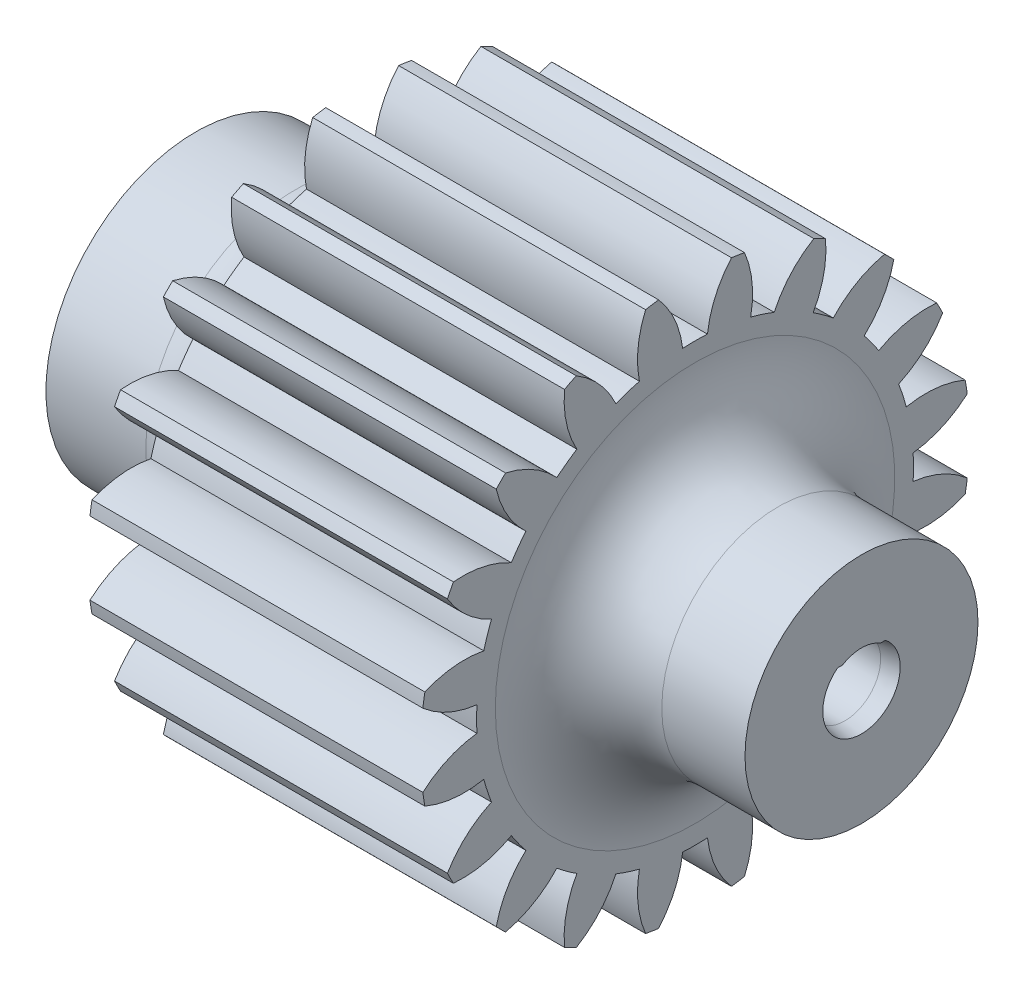
SolidWorks part; units mm, degrees
ref_plane "Plane1" through (0, 0, 0) normal (0, 0, 1) x (1, 0, 0)
ref_plane "Plane2" through (0, 0, 0) normal (0, 1, 0) x (1, 0, 0)
ref_plane "Plane3" through (0, 0, 0) normal (1, 0, 0) x (0, 0, -1)
other "Configuration Table"
sketch "HoldingSke" plane through (0, 0, 0) normal (0, 1, 0) x (1, 0, 0)
  line L0 (0, 0) -> (0.6265, -0.228)
  line L1 (-15, 0) -> (100, 0) construction
  line L2 (0, 0) -> (-2.1039, 2.3779)
  line L3 (0, 0) -> (-11.863, 4.5341)
  line L4 (0, 0) -> (8.1152, 2.9537)
  line L5 (0, 0) -> (-46.8476, -17.4728)
  line L6 (0, 0) -> (-16.5793, -11.1861)
  line L7 (-2.1039, 2.3779) -> (8.6586, 51.2059)
  line L8 (-76.2, 54.61) -> (-75.5, 54.61)
  line L9 (-71.009, 38.7566) -> (-53.1078, 45.2721)
  line L10 (-76.2, 71.12) -> (104.1128, 71.12)
  line L11 (0, 0) -> (-20, 0)
  line L12 (-76.2, 101.6) -> (-76.147, 101.6)
  line L13 (24.9733, 27.94) -> (52.9518, 28.4284)
  line L14 (24.9733, 27.94) -> (24.9743, 27.94)
  line L15 (24.9733, 27.94) -> (100.4006, 29.5858)
  line L16 (-63.627, -1.5) -> (-12.827, -1.5)
  circle A0 centre (0, 0) radius 2
  circle A1 centre (0, 0) radius 13.124
  circle A2 centre (0, 0) radius 37.5
  circle A3 centre (0, 0) radius 2
  dimension "Num_teeth" = 20
  dimension "Pitch_radius" = 180.3128
  dimension "Width" = 20
  dimension "Thickness" = 20
sketch "BasProSke" plane through (0, 0, 0) normal (0, 1, 0) x (1, 0, 0)
  line L0 (-10, 0) -> (60, 0) construction
  line L1 (0, 0) -> (0, 16.5)
  line L2 (0, 0) -> (20, 0)
  line L3 (20, 0) -> (20, 16.5)
  line L4 (20, 16.5) -> (0, 16.5)
  dimension "Thickness" = 20
  dimension "Diameter" = 33
revolve "Base-Revolve" add sketch "BasProSke" angle 360 about L0
sketch "TooCutSke" plane through (0, 0, 0) normal (1, 0, 0) x (0, 0, -1)
  line L1 (0, 0) -> (0, 107) construction
  line L2 (0, 0) -> (-1.2696, 14.9462) construction
  line L3 (0, 0) -> (-4.6808, 29.5532) construction
  line L4 (-1.2696, 14.9462) -> (-2.3404, 14.7766) construction
  arc A0 (0.7438, 13.1029) -> (-0.7438, 13.1029) centre (0, 0) ccw
  arc A1 (2.21, 16.377) -> (-2.21, 16.377) centre (0, 0) ccw
  circle A2 centre (0, 0) radius 15 construction
  circle A3 centre (0, 0) radius 14.0954 construction
  arc A4 (-0.7438, 13.1029) -> (-2.21, 16.377) centre (-6.7025, 12.3999) ccw
  arc A5 (2.21, 16.377) -> (0.7438, 13.1029) centre (6.7025, 12.3999) ccw
extrude "ToothCut" cut sketch "TooCutSke" along normal through all
fillet "Breaks" [suppressed] radius 0.03 tangent propagation no
fillet "RootFillets" [suppressed] radius 0.376
pattern_circular "TeethCuts" count 20 every 18 about axis through (-10, 0, 0) along (1, 0, 0) of "ToothCut", "RootFillets", "Breaks"
sketch "HubNeaOneSke" plane through (0, 0, 0) normal (-1, 0, 0) x (0, 0, 1)
  circle A0 centre (0, 0) radius 13.124
  dimension "Diameter" = 26.248
extrude "HubNearOne" [suppressed] add sketch "HubNeaOneSke" along normal blind 30.0001
sketch "HubNeaBotSke" plane through (0, 0, 0) normal (-1, 0, 0) x (0, 0, 1)
  circle A0 centre (0, 0) radius 13.124
  dimension "Diameter" = 26.248
extrude "HubNearBoth" [suppressed] add sketch "HubNeaBotSke" along normal blind 15
ref_plane "FarPln" through (20, 0, 0) normal (1, 0, 0) x (0, 0, -1)
sketch "HubFarSke" plane through (20, 0, 0) normal (1, 0, 0) x (0, 0, -1)
  circle A0 centre (0, 0) radius 13.124
  dimension "Diameter" = 26.248
extrude "HubFar" [suppressed] add sketch "HubFarSke" along normal blind 15
sketch "BorSke" plane through (0, 0, 0) normal (1, 0, 0) x (0, 0, -1)
  circle A0 centre (0, 0) radius 0.5
  dimension "Diameter" = 1
extrude "Bore" cut sketch "BorSke" along normal mid plane 100.0001
sketch "KeySke" plane through (0, 0, 0) normal (1, 0, 0) x (0, 0, -1)
  line L0 (-0.8, 0) -> (-0.8, 2.7)
  line L1 (-0.8, 2.7) -> (0.8, 2.7)
  line L2 (0.8, 2.7) -> (0.8, 0)
  line L3 (0, 0) -> (0, 34) construction
  line L4 (-0.8, 0) -> (0.8, 0)
  dimension "Width" = 1.6
extrude "Keyway" [suppressed] cut sketch "KeySke" along normal mid plane 100.0001
pattern_circular "Keyway2" [suppressed] count 2 every 90 about axis through (-10, 0, 0) along (1, 0, 0) reverse direction yes
sketch "Sketch1" plane through (20, 0, 0) normal (1, 0, 0) x (0, 0, -1)
  circle A0 centre (0, 0) radius 7
  circle A1 centre (0, 0) radius 0.5
  circle A2 centre (0, 0) radius 0.5 construction
  dimension "D1" = 14
extrude "Boss-Extrude1" add sketch "Sketch1" along normal blind 10
fillet "Fillet1" radius 5 1 edges at (20, 0, 7)
sketch "Sketch2" plane through (0, 0, 0) normal (-1, 0, 0) x (0, 0, 1)
  circle A0 centre (0, 0) radius 9
  dimension "D1" = 18
extrude "Boss-Extrude2" add sketch "Sketch2" along normal up to surface (10 mm away)
sketch "Sketch3" plane through (-10, 0, 0) normal (-1, 0, 0) x (0, 0, 1)
  circle A0 centre (0, 0) radius 3
  dimension "D1" = 6
extrude "Boss-Extrude3" add sketch "Sketch3" along normal up to surface (3.2 mm away)
fillet "Fillet2" radius 4 1 edges at (0, 0, -9)
sketch "Sketch4" plane through (30, 0, 0) normal (1, 0, 0) x (0, 0, -1)
  line L0 (-1.3229, 1.5) -> (1.3229, 1.5) construction
  line L1 (-1.3784, 1.65) -> (1.3784, 1.65)
  arc A2 (-1.3229, 1.5) -> (1.3229, 1.5) centre (0, 0) ccw construction
  arc A3 (-1.3784, 1.65) -> (1.3784, 1.65) centre (0, 0) ccw
  point P4 (0, -2)
  dimension "D1" = 4
  dimension "D2" = 3.5
  dimension "D3" = 0.15
extrude "Cut-Extrude1" cut sketch "Sketch4" against normal blind 25 contours A3 L1
chamfer "Chamfer2" distance 1 angle 10 2 edges at (30, -2.15, 0) (30, 1.65, 0) first distance on face at (17.5, -0.25, 0) first distance on face at (17.5, 1.65, 0)
sketch "Sketch5" plane through (30, 0, 0) normal (1, 0, 0) x (0, 0, -1)
  circle A0 centre (0, 0) radius 2.15
extrude "Cut-Extrude2" cut sketch "Sketch5" against normal blind 3
equation "' \"Module@HoldingSke\" = 6.35"
equation "' \"Num_teeth@HoldingSke\" = 12"
equation "' \"Ap@HoldingSke\" =  20"
equation "' \"Ap@HoldingSke\" = 20"
equation "' \"Width@HoldingSke\" = 0.5 * 25.4"
equation "' \"Hub_dia@HoldingSke\"= 1 * 25.4"
equation "' \"Hub_dia@HoldingSke\" = 1 * 25.4"
equation "' \"Overall_len@HoldingSke\" = 1.0 * 25.4"
equation "' \"Bore@HoldingSke\" = 0.75 * 25.4"
equation "' \"T_dim@HoldingSke\" = 0.1 * 25.4"
equation "' \"Width@KeySke\" = 0.25 * 25.4"
equation "' \"Show_teeth@HoldingSke\" = 13"
equation "' \"Backlash@HoldingSke\" = 0.009 * 25.4"
equation "' \"Addendum_fac@HoldingSke\" = 1.0"
equation "' \"Dedendum_fac@HoldingSke\" = 1.25"
equation "' \"Dedendum_add@HoldingSke\" = 0.00005 * 25.4"
equation "' \"Clearance_fac@HoldingSke\" = 0.25"
equation "\"Pitch@HoldingSke\" = 1 / \"Module@HoldingSke\""
equation "\"Overcut_dia@TooCutSke\" = (\"Num_teeth@HoldingSke\" + 2 * \"Addendum_fac@HoldingSke\") / \"Pitch@HoldingSke\" + 0.002 * 25.4"
equation "\"Pitch_dia@TooCutSke\" = \"Num_teeth@HoldingSke\" / \"Pitch@HoldingSke\""
equation "\"Base_dia@TooCutSke\" = \"Num_teeth@HoldingSke\" / \"Pitch@HoldingSke\" * cos((\"Ap@HoldingSke\"  * 3.14159265 / 180))"
equation "\"Root_dia@TooCutSke\" = (\"Num_teeth@HoldingSke\" + 2) / \"Pitch@HoldingSke\" - 2 * (\"Addendum_fac@HoldingSke\" + \"Dedendum_fac@HoldingSke\") / \"Pitch@HoldingSke\" - \"Dedendum_add@HoldingSke\" * 2"
equation "\"Half_ang@TooCutSke\" = 180 / \"Num_teeth@HoldingSke\""
equation "\"Half_CT@TooCutSke\" = \"Num_teeth@HoldingSke\" / \"Pitch@HoldingSke\" * sin((3.14159265 / 2 / \"Num_teeth@HoldingSke\")) / 2 - 7 * \"Backlash@HoldingSke\" / 4"
equation "\"Flank_rad@TooCutSke\" = \"Num_teeth@HoldingSke\" / \"Pitch@HoldingSke\" / 5"
equation "\"Radius@RootFillets\" = \"Clearance_fac@HoldingSke\" / \"Pitch@HoldingSke\" + \"Dedendum_add@HoldingSke\""
equation "\"Break_rad@Breaks\" = 0.02 / \"Pitch@HoldingSke\""
equation "\"Thickness@HoldingSke\" = \"Width@HoldingSke\""
equation "\"OAL@HoldingSke\" = \"Thickness@HoldingSke\""
equation "\"MHD@HoldingSke\" = (\"Num_teeth@HoldingSke\" + 2) / \"Pitch@HoldingSke\" - 2 * (\"Addendum_fac@HoldingSke\" + \"Dedendum_fac@HoldingSke\")  / \"Pitch@HoldingSke\" - \"Dedendum_add@HoldingSke\" * 2"
equation "\"MBD@HoldingSke\" = (\"Num_teeth@HoldingSke\" + 2) / \"Pitch@HoldingSke\" - 2 * (\"Addendum_fac@HoldingSke\" + \"Dedendum_fac@HoldingSke\")  / \"Pitch@HoldingSke\" - \"Dedendum_add@HoldingSke\" * 2 - 0.002 * 25.4"
equation "\"MHD@HoldingSke\" = ((sgn( \"MHD@HoldingSke\" - \"Hub_dia@HoldingSke\" )-1)*( \"MHD@HoldingSke\" - \"Hub_dia@HoldingSke\" ))/-2+ \"Hub_dia@HoldingSke\""
equation "\"MBD@HoldingSke\" = ((sgn( \"MBD@HoldingSke\" - \"Bore@HoldingSke\" )-1)*( \"MBD@HoldingSke\" - \"Bore@HoldingSke\" ))/-2+ \"Bore@HoldingSke\""
equation "\"OAL@HoldingSke\" = ((sgn( \"OAL@HoldingSke\" - \"Overall_len@HoldingSke\" )+1)*( \"OAL@HoldingSke\" - \"Overall_len@HoldingSke\" ))/2 + \"Overall_len@HoldingSke\" + 0.000002 * 25.4"
equation "\"Num_teeth@TeethCuts\" = int( \"Show_teeth@HoldingSke\" ) + 1"
equation "\"Num_teeth@TeethCuts\" = ((sgn( \"Num_teeth@TeethCuts\" - \"Num_teeth@HoldingSke\" )-1)*( \"Num_teeth@TeethCuts\" - \"Num_teeth@HoldingSke\" ))/-2+ \"Num_teeth@HoldingSke\""
equation "\"Num_teeth@TeethCuts\" = ((sgn( \"Num_teeth@TeethCuts\" - 2.0)+1)*( \"Num_teeth@TeethCuts\" - 2.0))/2 +2.0"
equation "\"Angle@TeethCuts\" = 360.0 / \"Num_teeth@HoldingSke\""
equation "\"Diameter@BasProSke\" = (\"Num_teeth@HoldingSke\" + 2 * \"Addendum_fac@HoldingSke\") / \"Pitch@HoldingSke\""
equation "\"Thickness@BasProSke\"  = \"Thickness@HoldingSke\""
equation "' \"Fillet_rad@BasProSke\" =  \"Thickness@HoldingSke\" * 0.05"
equation "' \"Fillet_rad@BasProSke\" = \"Thickness@HoldingSke\" * 0.05"
equation "\"MHD@HoldingSke\" = ((sgn( \"MHD@HoldingSke\" - \"Root_dia@TooCutSke\" )-1)*( \"MHD@HoldingSke\" - \"Root_dia@TooCutSke\" ))/-2+ \"Root_dia@TooCutSke\""
equation "\"Diameter@HubNeaOneSke\" = \"MHD@HoldingSke\""
equation "\"Length@HubNearOne\" = \"OAL@HoldingSke\" - \"Thickness@BasProSke\""
equation "\"Diameter@HubNeaBotSke\" = \"MHD@HoldingSke\""
equation "\"Length@HubNearBoth\" = ( \"OAL@HoldingSke\" - \"Thickness@BasProSke\" ) / 2.0"
equation "\"Thickness@FarPln\" = \"Thickness@BasProSke\""
equation "\"Diameter@HubFarSke\" = \"MHD@HoldingSke\""
equation "\"Length@HubFar\" = ( \"OAL@HoldingSke\" - \"Thickness@BasProSke\" ) / 2.0"
equation "\"D1@Bore\" = \"OAL@HoldingSke\" * 2.0"
equation "\"D1@Keyway\" = \"OAL@HoldingSke\" * 2.0"
equation "\"Offset@KeySke\" = \"T_dim@HoldingSke\" + \"MBD@HoldingSke\" / 2.0"
